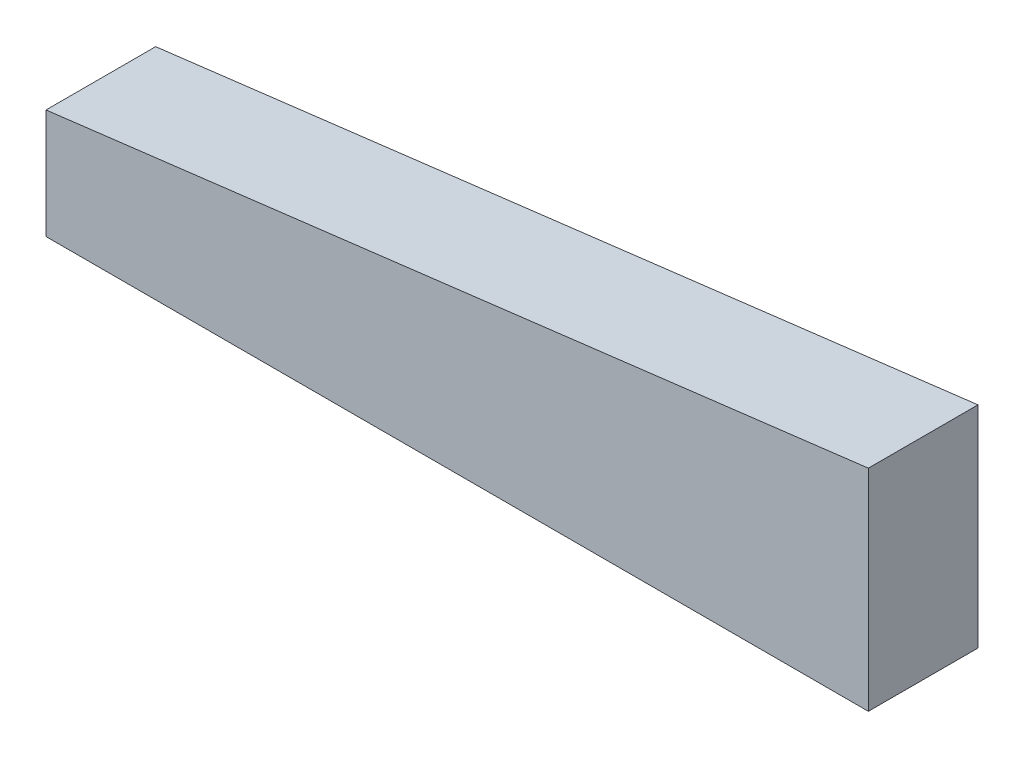
SolidWorks part; units mm, degrees
ref_plane "Front Plane" through (0, 0, 0) normal (0, 0, 1) x (1, 0, 0)
ref_plane "Top Plane" through (0, 0, 0) normal (0, 1, 0) x (1, 0, 0)
ref_plane "Right Plane" through (0, 0, 0) normal (1, 0, 0) x (0, 0, -1)
sketch "Sketch1" plane through (0, 0, 0) normal (0, 1, 0) x (1, 0, 0)
  line L1 (-75, -10) -> (75, -10)
  line L2 (-75, -10) -> (-75, 10)
  line L3 (-75, 10) -> (75, 10)
  line L4 (75, -10) -> (75, 10)
  line L5 (-75, -10) -> (75, 10) construction
  line L6 (-75, 10) -> (75, -10) construction
  point P0 (0, 0)
  dimension "D1" = 20
  dimension "D2" = 150
extrude "Boss-Extrude1" add sketch "Sketch1" along normal mid plane 20
sketch "Sketch2" plane through (0, 0, 0) normal (0, 0, 1) x (1, 0, 0)
  line L0 (-75, 10) -> (75, 10)
  line L1 (75, 10) -> (75, 28.4177)
  line L2 (75, 28.4177) -> (-75, 10)
  dimension "D1" = 7
extrude "Boss-Extrude2" add sketch "Sketch2" along normal mid plane 20
